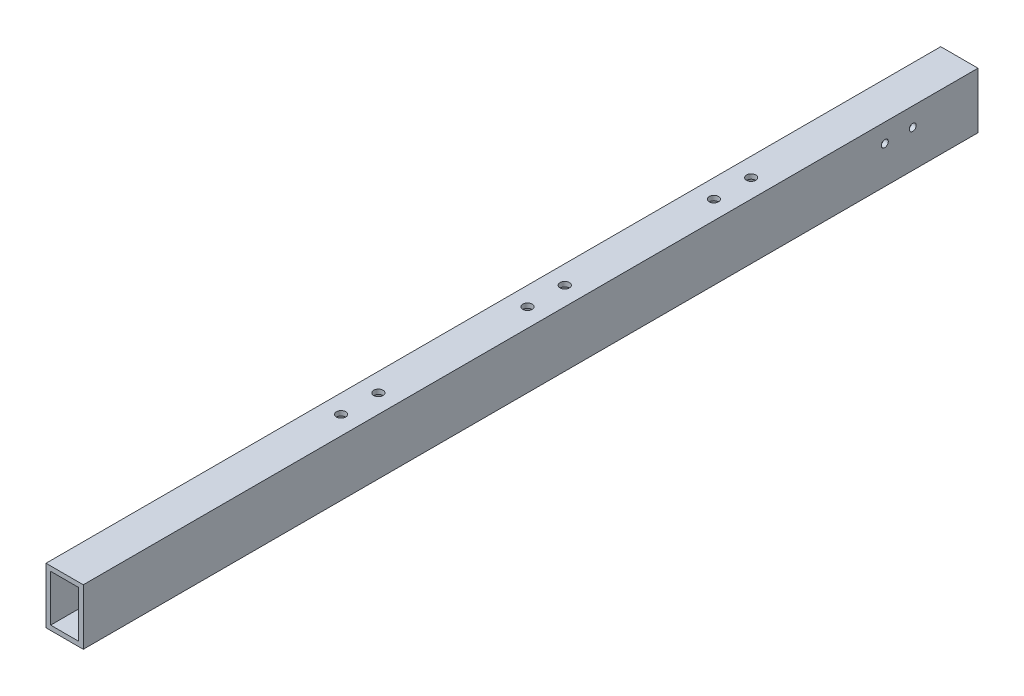
SolidWorks part; units mm, degrees
material "6063-T1"
ref_plane "Front Plane" through (0, 0, 0) normal (0, 0, 1) x (1, 0, 0)
ref_plane "Top Plane" through (0, 0, 0) normal (0, 1, 0) x (1, 0, 0)
ref_plane "Right Plane" through (0, 0, 0) normal (1, 0, 0) x (0, 0, -1)
sketch "Sketch1" plane through (0, 0, 0) normal (0, 0, 1) x (1, 0, 0)
  line L1 (-12.7, 19.05) -> (12.7, 19.05)
  line L2 (-12.7, 19.05) -> (-12.7, -19.05)
  line L3 (-12.7, -19.05) -> (12.7, -19.05)
  line L4 (12.7, 19.05) -> (12.7, -19.05)
  line L5 (-12.7, 19.05) -> (12.7, -19.05) construction
  line L6 (-12.7, -19.05) -> (12.7, 19.05) construction
  point P0 (0, 0)
  dimension "D1" = 25.4
  dimension "D2" = 38.1
extrude "Boss-Extrude1" add sketch "Sketch1" along normal blind 609.6
shell "Shell1" thickness 3.175 removed face at (0, 0, 0) removed face at (0, 0, 609.6)
sketch "Sketch2" plane through (12.7, 0, 0) normal (1, 0, 0) x (0, 0, -1)
  line L0 (0, -19.05) -> (0, 19.05) construction
  line L1 (-609.6, -19.05) -> (0, -19.05) construction
  circle A0 centre (-44.45, 6.35) radius 2.3812
  circle A1 centre (-63.5, 6.35) radius 2.3812
  dimension "D2" = 4.7625
  dimension "D5" = 4.7625
  dimension "D1" = 44.45
  dimension "D3" = 25.4
  dimension "D4" = 19.05
  dimension "D6" = 25.4
extrude "Cut-Extrude1" cut sketch "Sketch2" against normal through all
sketch "Sketch3" plane through (0, 19.05, 0) normal (0, 1, 0) x (1, 0, 0)
  line L0 (0, -294.2559) -> (0, -268.8559) construction
  line L1 (0, -408.5559) -> (0, -154.5559) construction
  line L2 (0, -167.2559) -> (0, -141.8559) construction
  line L3 (0, -421.2559) -> (0, -395.8559) construction
  circle A0 centre (0, -268.8559) radius 3.175
  circle A1 centre (0, -294.2559) radius 3.175
  circle A2 centre (0, -141.8559) radius 3.175
  circle A3 centre (0, -167.2559) radius 3.175
  circle A4 centre (0, -395.8559) radius 3.175
  circle A5 centre (0, -421.2559) radius 3.175
  point P4 (0, -281.5559)
  point P9 (0, -281.5559)
  point P12 (0, -154.5559)
  point P17 (0, -408.5559)
  dimension "D2" = 6.35
  dimension "D3" = 6.35
  dimension "D6" = 6.35
  dimension "D7" = 6.35
  dimension "D9" = 6.35
  dimension "D10" = 6.35
  dimension "D1" = 12.7
  dimension "D4" = 127
  dimension "D5" = 12.7
  dimension "D8" = 12.7
extrude "Cut-Extrude2" cut sketch "Sketch3" against normal up to surface (34.925 mm away) up to face at (0, -15.875, 304.8)
